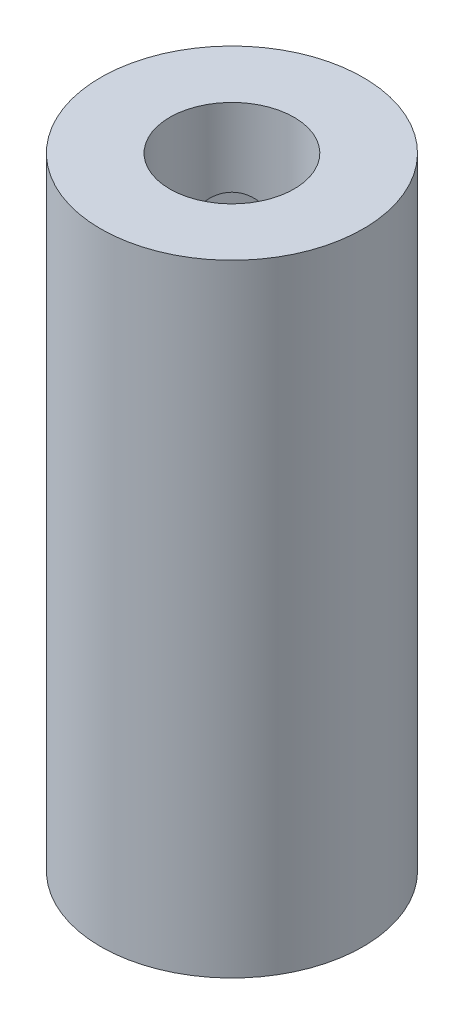
SolidWorks part; units mm, degrees
material "Polyurethane Foam Flexible"
ref_plane "Front Plane" through (0, 0, 0) normal (0, 0, 1) x (1, 0, 0)
ref_plane "Top Plane" through (0, 0, 0) normal (0, 1, 0) x (1, 0, 0)
ref_plane "Right Plane" through (0, 0, 0) normal (1, 0, 0) x (0, 0, -1)
sketch "Sketch1" plane through (0, 0, 0) normal (0, 1, 0) x (1, 0, 0)
  circle A0 centre (0, 0) radius 48.26
  dimension "D1" = 96.52
extrude "Boss-Extrude1" add sketch "Sketch1" along normal blind 228.6 contours A0
shell "Shell1" thickness 25.4 removed face at (0, 228.6, 48.26)
sketch "Sketch4" plane through (0, 0, 0) normal (0, 0, 1) x (1, 0, 0)
  line L0 (48.26, 0) -> (48.26, 228.6) construction
  line L1 (0, 0) -> (0, 228.6) construction
  line L2 (22.86, 228.6) -> (-22.86, 228.6) construction
  circle A0 centre (0, 38.1) radius 12.7
  dimension "D1" = 25.4
  dimension "D2" = 38.1
  dimension "D3" = 48.26
extrude "Cut-Extrude9" cut sketch "Sketch4" along normal blind 45.72 and the other way blind 45.72
pattern_linear "LPattern1" count 5 spacing 37.3 along (0, 1, 0) of "Cut-Extrude9"
pattern_circular "CirPattern1" count 4 every 45 about axis through (0, 228.6, 0) along (0, -1, 0) of "LPattern1"
